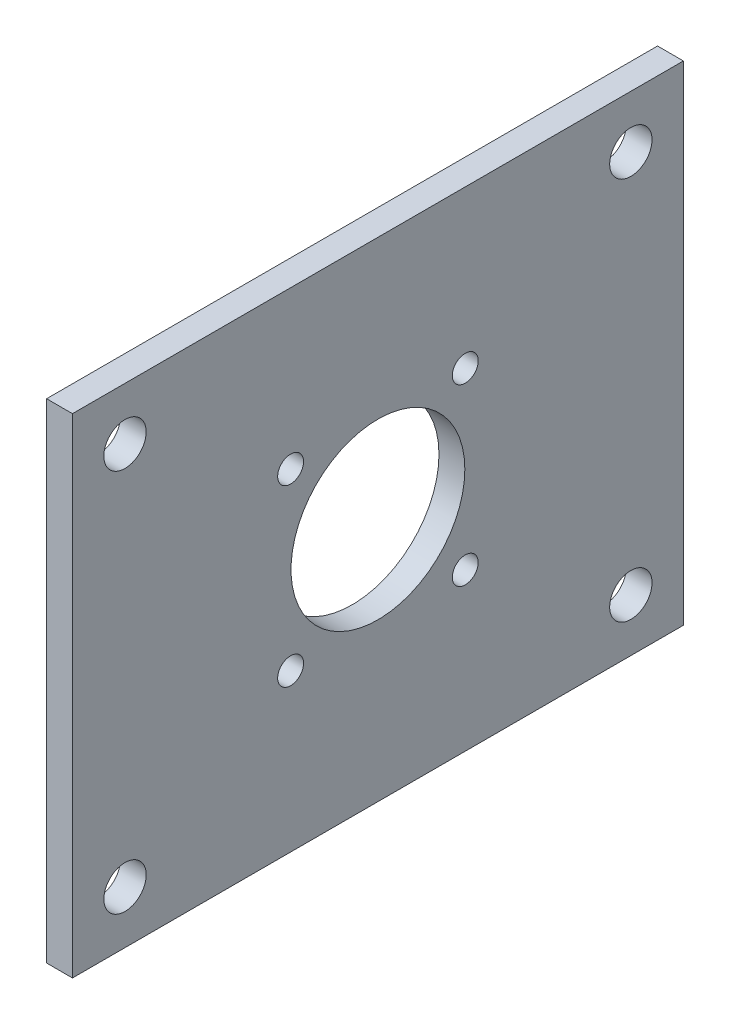
SolidWorks part; units mm, degrees
ref_plane "Front Plane" through (0, 0, 0) normal (0, 0, 1) x (1, 0, 0)
ref_plane "Top Plane" through (0, 0, 0) normal (0, 1, 0) x (1, 0, 0)
ref_plane "Right Plane" through (0, 0, 0) normal (1, 0, 0) x (0, 0, -1)
sketch "Sketch1" plane through (0, 0, 0) normal (1, 0, 0) x (0, 0, -1)
  line L1 (-37.5, -30) -> (37.5, -30)
  line L2 (-37.5, -30) -> (-37.5, 30)
  line L3 (-37.5, 30) -> (37.5, 30)
  line L4 (37.5, -30) -> (37.5, 30)
  line L5 (-37.5, -30) -> (37.5, 30) construction
  line L6 (-37.5, 30) -> (37.5, -30) construction
  point P0 (0, 0)
  dimension "D1" = 75
  dimension "D2" = 60
extrude "Boss-Extrude1" add sketch "Sketch1" along normal blind 1.5875 and the other way blind 1.5875
sketch "Sketch2" plane through (0, 0, 0) normal (1, 0, 0) x (0, 0, -1)
  line L0 (-37.5, 30) -> (-31.05, 30) construction
  line L1 (37.5, 30) -> (-37.5, 30) construction
  line L2 (-31.05, 30) -> (-31.05, 23.55) construction
  line L3 (0, 1.7463) -> (0, -1.7463) construction
  line L4 (1.7463, 0) -> (-1.7463, 0) construction
  circle A0 centre (-31.05, 23.55) radius 2.6
  circle A1 centre (31.05, 23.55) radius 2.6
  circle A2 centre (31.05, -23.55) radius 2.6
  circle A3 centre (-31.05, -23.55) radius 2.6
  dimension "D3" = 5.2
  dimension "D1" = 6.45
  dimension "D2" = 6.45
extrude "Cut-Extrude1" cut sketch "Sketch2" against normal through all both and the other way through all
sketch "Sketch3" plane through (0, 0, 0) normal (1, 0, 0) x (0, 0, -1)
  line L0 (0, 1.7463) -> (0, -1.7463) construction
  line L1 (-10.72, 10.72) -> (10.72, 10.72) construction
  line L2 (-10.72, 10.72) -> (-10.72, -10.72) construction
  line L3 (-10.72, -10.72) -> (10.72, -10.72) construction
  line L4 (10.72, 10.72) -> (10.72, -10.72) construction
  line L5 (-10.72, 10.72) -> (10.72, -10.72) construction
  line L6 (-10.72, -10.72) -> (10.72, 10.72) construction
  line L7 (1.7463, 0) -> (-1.7463, 0) construction
  circle A0 centre (0, 0) radius 10.67
  circle A1 centre (-10.72, 10.72) radius 1.59
  circle A2 centre (10.72, 10.72) radius 1.59
  circle A3 centre (10.72, -10.72) radius 1.59
  circle A4 centre (-10.72, -10.72) radius 1.59
  dimension "D1" = 3.18
  dimension "D2" = 21.34
  dimension "D3" = 21.44
  dimension "D4" = 21.44
extrude "Cut-Extrude2" cut sketch "Sketch3" against normal through all both and the other way through all
